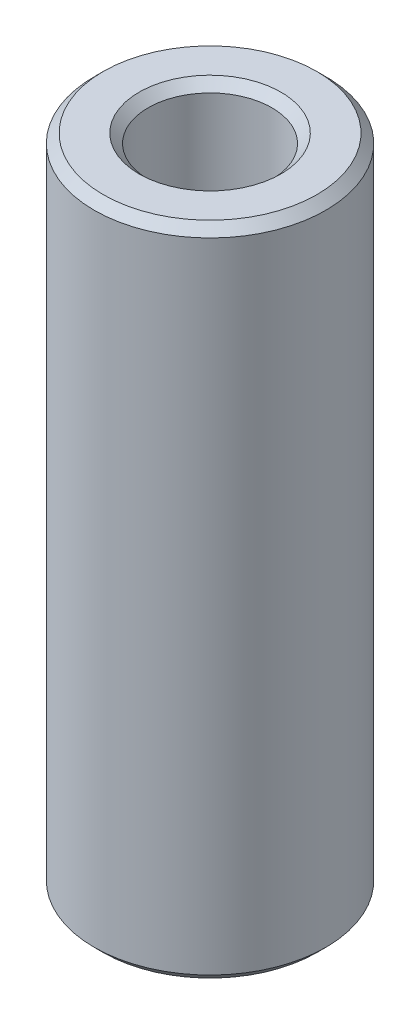
SolidWorks part; units mm, degrees
ref_plane "Front Plane" through (0, 0, 0) normal (0, 0, 1) x (1, 0, 0)
ref_plane "Top Plane" through (0, 0, 0) normal (0, 1, 0) x (1, 0, 0)
ref_plane "Right Plane" through (0, 0, 0) normal (1, 0, 0) x (0, 0, -1)
sketch "Sketch1" plane through (0, 0, 0) normal (0, 1, 0) x (1, 0, 0)
  circle A0 centre (0, 0) radius 37.5
  dimension "SLEEVE_OD" = 75
extrude "Boss-Extrude1" add sketch "Sketch1" along normal blind 212.585
sketch "Sketch2" plane through (0, 0, 0) normal (0, 1, 0) x (1, 0, 0)
  circle A0 centre (0, 0) radius 20.0511
  dimension "BORE_D" = 40.1021
extrude "Cut-Extrude1" cut sketch "Sketch2" along normal through all
chamfer "Chamfer1" distance 2.9186 angle 45 4 edges at (0, 212.585, 20.0511) (0, 0, 20.0511) (0, 0, 37.5) (0, 212.585, 37.5)
